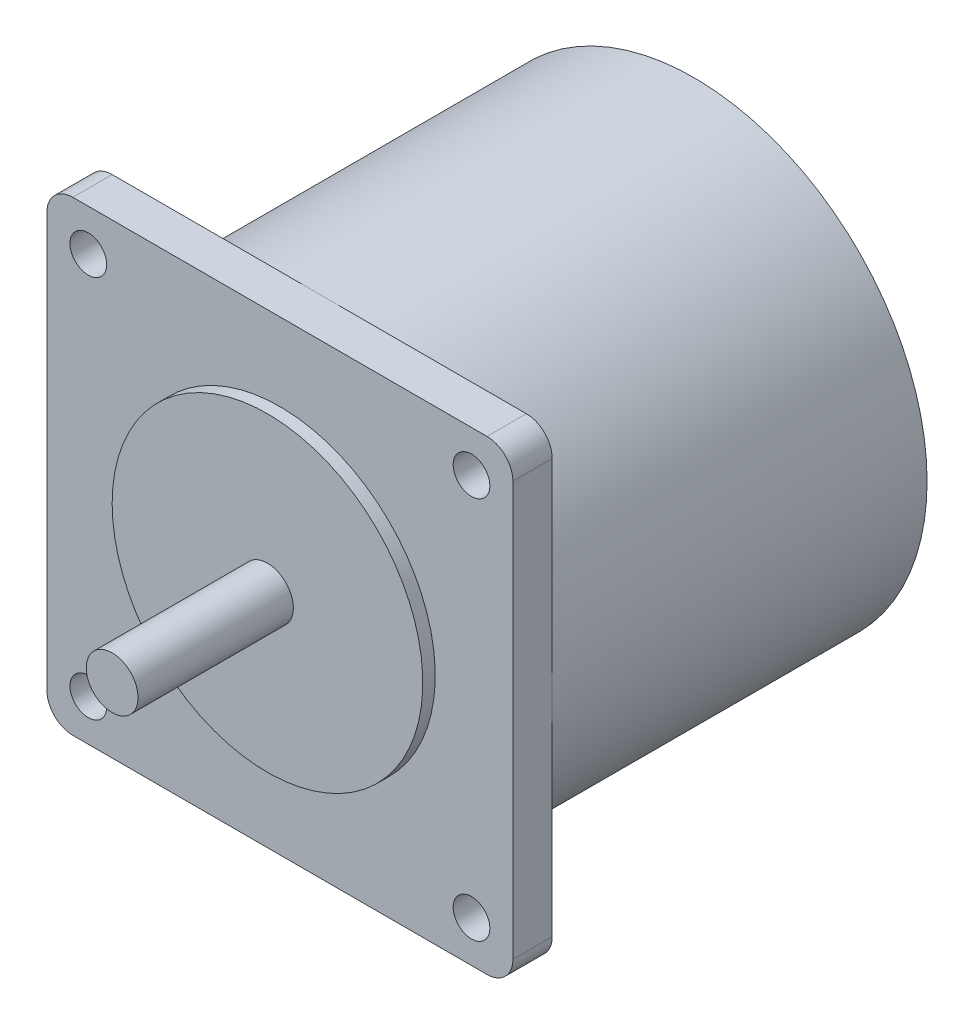
SolidWorks part; units mm, degrees
ref_plane "Front Plane" through (0, 0, 0) normal (0, 0, 1) x (1, 0, 0)
ref_plane "Top Plane" through (0, 0, 0) normal (0, 1, 0) x (1, 0, 0)
ref_plane "Right Plane" through (0, 0, 0) normal (1, 0, 0) x (0, 0, -1)
sketch "Sketch1" plane through (0, 0, 0) normal (0, 0, 1) x (1, 0, 0)
  line L1 (-28.575, -28.575) -> (28.575, -28.575)
  line L2 (-28.575, -28.575) -> (-28.575, 28.575)
  line L3 (-28.575, 28.575) -> (28.575, 28.575)
  line L4 (28.575, -28.575) -> (28.575, 28.575)
  line L5 (-28.575, -28.575) -> (28.575, 28.575) construction
  line L6 (-28.575, 28.575) -> (28.575, -28.575) construction
  point P0 (0, 0)
  dimension "D1" = 57.15
extrude "Boss-Extrude1" add sketch "Sketch1" against normal blind 4.826
sketch "Sketch2" plane through (0, 0, 0) normal (0, 0, 1) x (1, 0, 0)
  circle A0 centre (0, 0) radius 19.05
  dimension "D1" = 38.1
extrude "Boss-Extrude2" add sketch "Sketch2" along normal blind 1.524
sketch "Sketch3" plane through (0, 0, 0) normal (0, 0, 1) x (1, 0, 0)
  circle A0 centre (0, 0) radius 3.175
  dimension "D1" = 6.35
extrude "Boss-Extrude3" add sketch "Sketch3" along normal blind 20.574
sketch "Sketch5" plane through (0, 0, 0) normal (0, 0, 1) x (1, 0, 0)
  line L0 (28.575, 28.575) -> (-28.575, 28.575) construction
  circle A0 centre (0, 0) radius 28.575
extrude "Boss-Extrude4" add sketch "Sketch5" against normal blind 50.8
hole_wizard "M4 Clearance Hole1" positions "Sketch6" profile "Sketch8" hole size "M4" standard "ANSI Metric" end condition up to next
sketch "Sketch6" plane through (0, 0, 0) normal (0, 0, 1) x (1, 0, 0)
  line L0 (-23.5, -23.5) -> (-23.5, 23.5) construction
  line L1 (-23.5, 23.5) -> (23.5, 23.5) construction
  line L2 (23.5, 23.5) -> (23.5, -23.5) construction
  line L3 (23.5, -23.5) -> (-23.5, -23.5) construction
  line L5 (0, 0) -> (23.5, 0) construction
  line L7 (0, 23.5) -> (0, 0) construction
  point P0 (-23.5, 23.5)
  point P2 (23.5, 23.5)
  point P4 (23.5, -23.5)
  point P6 (-23.5, -23.5)
  dimension "D1" = 47
sketch "Sketch8" plane through (-23.5, 23.5, 0) normal (1, 0, 0) x (0, -1, 0)
  line L0 (0, 0) -> (0, 4.826)
  line L1 (0, 4.826) -> (2.25, 4.826)
  line L2 (2.25, 4.826) -> (2.25, 0)
  line L5 (2.25, 0) -> (0, 0)
  line L11 (0, -6.35) -> (0, 107.95) construction
  dimension "Thru Hole Dia." = 4.5
  dimension "Thru Hole Depth" = 4.826
fillet "Fillet1" radius 3.175 4 edges at (-28.575, -28.575, -2.413) (-28.575, 28.575, -2.413) (28.575, -28.575, -2.413) (28.575, 28.575, -2.413)
